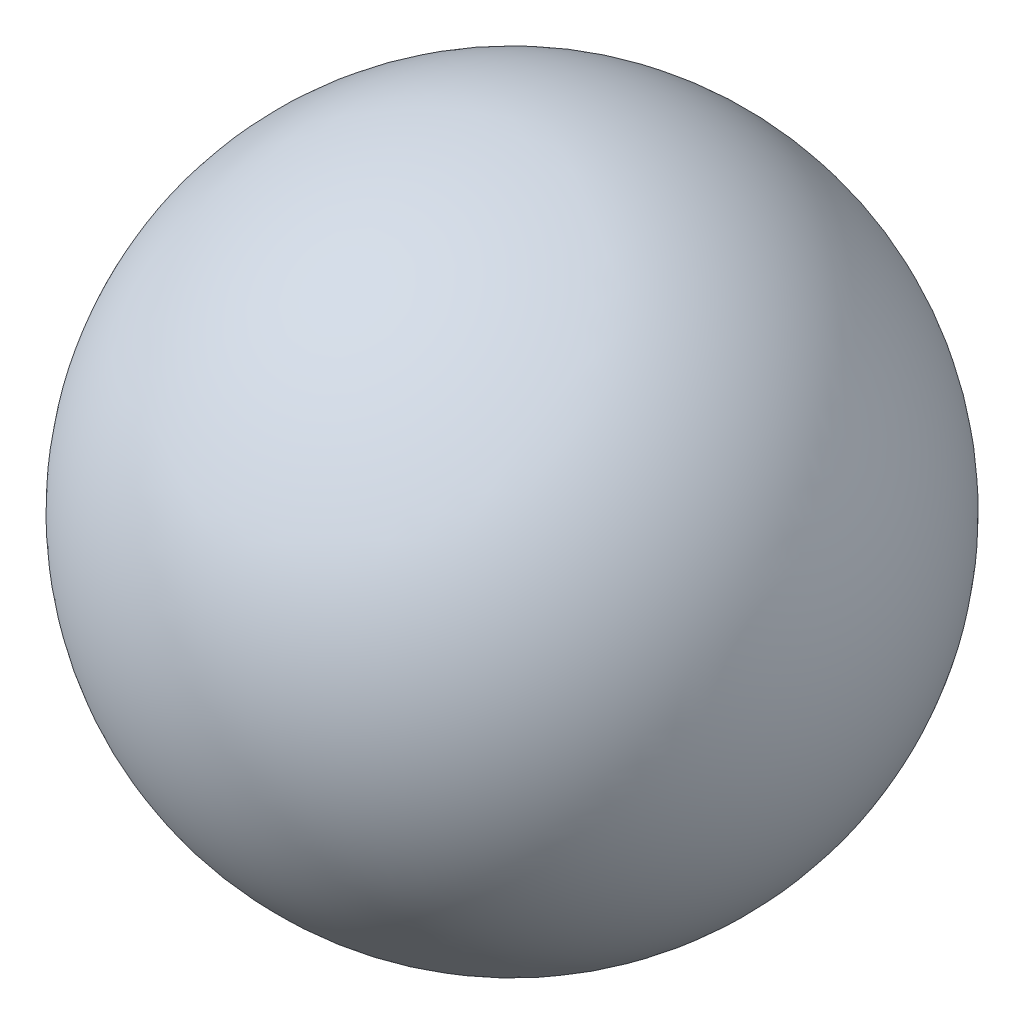
SolidWorks part; units mm, degrees
ref_plane "Front Plane" through (0, 0, 0) normal (0, 0, 1) x (1, 0, 0)
ref_plane "Top Plane" through (0, 0, 0) normal (0, 1, 0) x (1, 0, 0)
ref_plane "Right Plane" through (0, 0, 0) normal (1, 0, 0) x (0, 0, -1)
sketch "Sketch2" plane through (0, 0, 0) normal (0, 0, 1) x (1, 0, 0)
  line L0 (452.2664, 0) -> (-452.2664, 0)
  arc A0 (452.2664, 0) -> (-452.2664, 0) centre (0, 0) ccw
  dimension "D1" = 904.5329
revolve "Revolve1" add sketch "Sketch2" angle 360 about L0
